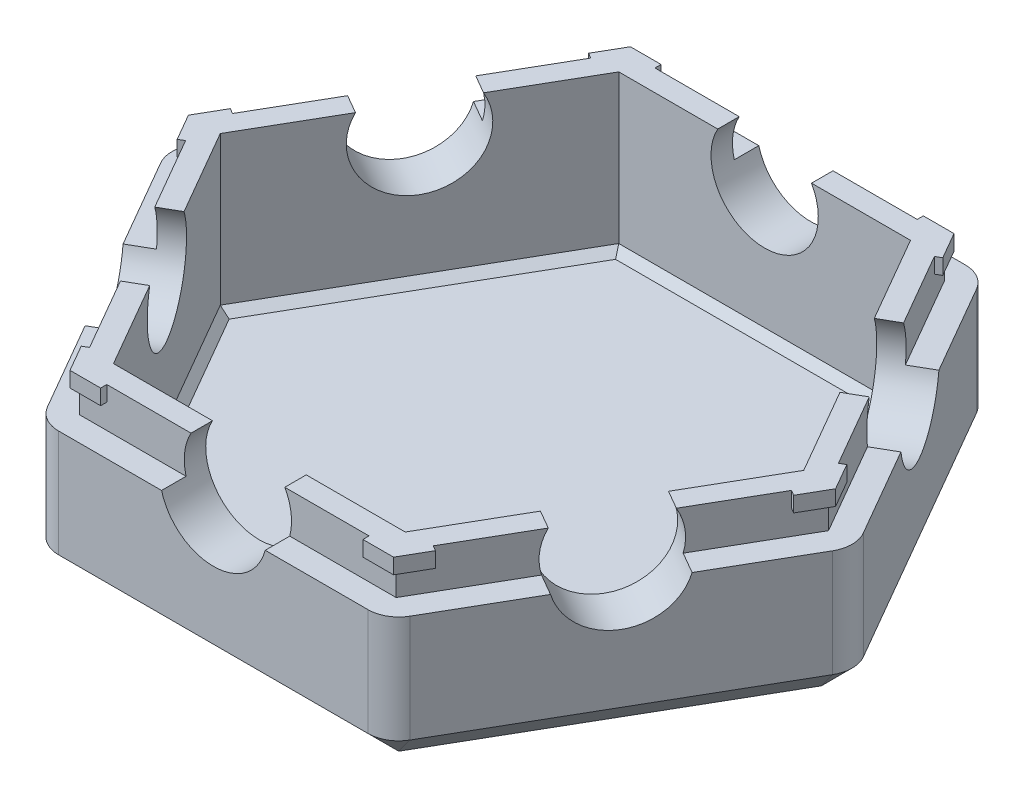
SolidWorks part; units mm, degrees
ref_plane "Front Plane" through (0, 0, 0) normal (0, 0, 1) x (1, 0, 0)
ref_plane "Top Plane" through (0, 0, 0) normal (0, 1, 0) x (1, 0, 0)
ref_plane "Right Plane" through (0, 0, 0) normal (1, 0, 0) x (0, 0, -1)
sketch "Sketch1" plane through (0, 0, 0) normal (0, 1, 0) x (1, 0, 0)
  line L0 (22.5, 0) -> (0, 0) construction
  line L1 (22.5, 0) -> (11.25, 19.4856)
  line L2 (11.25, 19.4856) -> (-11.25, 19.4856)
  line L3 (-11.25, 19.4856) -> (-22.5, 0)
  line L4 (-22.5, 0) -> (-11.25, -19.4856)
  line L5 (-11.25, -19.4856) -> (11.25, -19.4856)
  line L6 (11.25, -19.4856) -> (22.5, 0)
  circle A0 centre (0, 0) radius 19.4856 construction
  dimension "D1" = 22.5
extrude "Boss-Extrude1" add sketch "Sketch1" against normal blind 10 from offset 3.7 offset against normal yes
sketch "Sketch2" plane through (0, -3.7, 0) normal (0, 1, 0) x (1, 0, 0)
  line L0 (19.0359, 0) -> (9.5179, 16.4856)
  line L1 (9.5179, 16.4856) -> (-9.5179, 16.4856)
  line L2 (-9.5179, 16.4856) -> (-19.0359, 0)
  line L3 (-19.0359, 0) -> (-9.5179, -16.4856)
  line L4 (-9.5179, -16.4856) -> (9.5179, -16.4856)
  line L5 (9.5179, -16.4856) -> (19.0359, 0)
  line L6 (11.25, -19.4856) -> (22.5, 0)
  line L7 (22.5, 0) -> (11.25, 19.4856)
  line L8 (11.25, 19.4856) -> (-11.25, 19.4856)
  line L9 (-11.25, 19.4856) -> (-22.5, 0)
  line L10 (-22.5, 0) -> (-11.25, -19.4856)
  line L11 (-11.25, -19.4856) -> (11.25, -19.4856)
  line L12 (11.25, -19.4856) -> (22.5, 0)
  line L13 (22.5, 0) -> (11.25, 19.4856)
  line L14 (11.25, 19.4856) -> (-11.25, 19.4856)
  line L15 (-11.25, 19.4856) -> (-22.5, 0)
  line L16 (-22.5, 0) -> (-11.25, -19.4856)
  line L17 (-11.25, -19.4856) -> (11.25, -19.4856)
  dimension "D1" = 0
  dimension "D2" = 3
extrude "Cut-Extrude1" cut sketch "Sketch2" against normal blind 8.6 contours L4 L5 L0 L1 L2 L3 region at (0, -3.7, 0)
sketch "Sketch3" plane through (0, -3.7, 0) normal (0, 1, 0) x (1, 0, 0)
  line L0 (10.3262, -17.8856) -> (20.6525, 0)
  line L1 (20.6525, 0) -> (10.3262, 17.8856)
  line L2 (10.3262, 17.8856) -> (-10.3262, 17.8856)
  line L3 (-10.3262, 17.8856) -> (-20.6525, 0)
  line L4 (-20.6525, 0) -> (-10.3262, -17.8856)
  line L5 (-10.3262, -17.8856) -> (10.3262, -17.8856)
  line L6 (-9.5179, -16.4856) -> (9.5179, -16.4856)
  line L7 (-19.0359, 0) -> (-9.5179, -16.4856)
  line L8 (-9.5179, 16.4856) -> (-19.0359, 0)
  line L9 (9.5179, 16.4856) -> (-9.5179, 16.4856)
  line L10 (19.0359, 0) -> (9.5179, 16.4856)
  line L11 (9.5179, -16.4856) -> (19.0359, 0)
  line L12 (-9.5179, -16.4856) -> (9.5179, -16.4856)
  line L13 (-19.0359, 0) -> (-9.5179, -16.4856)
  line L14 (-9.5179, 16.4856) -> (-19.0359, 0)
  line L15 (9.5179, 16.4856) -> (-9.5179, 16.4856)
  line L16 (19.0359, 0) -> (9.5179, 16.4856)
  line L17 (9.5179, -16.4856) -> (19.0359, 0)
  dimension "D1" = 0
  dimension "D2" = 1.4
extrude "Boss-Extrude2" add sketch "Sketch3" along normal blind 1.6
fillet "Fillet1" radius 2 6 edges at (22.5, -8.7, 0) (11.25, -8.7, 19.4856) (-11.25, -8.7, 19.4856) (-22.5, -8.7, 0) (-11.25, -8.7, -19.4856) (11.25, -8.7, -19.4856)
sketch "Sketch6" plane through (0, -3.7, 0) normal (0, 1, 0) x (1, 0, 0)
  line L6 (10.3262, -17.8856) -> (20.6525, 0)
  line L7 (-10.3262, -17.8856) -> (10.3262, -17.8856)
  line L8 (-20.6525, 0) -> (-10.3262, -17.8856)
  line L9 (-10.3262, 17.8856) -> (-20.6525, 0)
  line L10 (10.3262, 17.8856) -> (-10.3262, 17.8856)
  line L11 (20.6525, 0) -> (10.3262, 17.8856)
  line L12 (10.3262, -17.8856) -> (20.6525, 0)
  line L13 (-10.3262, -17.8856) -> (10.3262, -17.8856)
  line L14 (-20.6525, 0) -> (-10.3262, -17.8856)
  line L15 (-10.3262, 17.8856) -> (-20.6525, 0)
  line L16 (10.3262, 17.8856) -> (-10.3262, 17.8856)
  line L17 (20.6525, 0) -> (10.3262, 17.8856)
  line L18 (11.8274, -18.4856) -> (21.9226, -1)
  line L19 (21.9226, 1) -> (11.8274, 18.4856)
  line L20 (10.0953, 19.4856) -> (-10.0953, 19.4856)
  line L21 (-11.8274, 18.4856) -> (-21.9226, 1)
  line L22 (-21.9226, -1) -> (-11.8274, -18.4856)
  line L23 (-10.0953, -19.4856) -> (10.0953, -19.4856)
  line L24 (11.8274, -18.4856) -> (21.9226, -1)
  line L25 (21.9226, 1) -> (11.8274, 18.4856)
  line L26 (10.0953, 19.4856) -> (-10.0953, 19.4856)
  line L27 (-11.8274, 18.4856) -> (-21.9226, 1)
  line L28 (-21.9226, -1) -> (-11.8274, -18.4856)
  line L29 (-10.0953, -19.4856) -> (10.0953, -19.4856)
  arc A6 (21.9226, -1) -> (21.9226, 1) centre (20.1906, 0) ccw
  arc A7 (11.8274, 18.4856) -> (10.0953, 19.4856) centre (10.0953, 17.4856) ccw
  arc A8 (-10.0953, 19.4856) -> (-11.8274, 18.4856) centre (-10.0953, 17.4856) ccw
  arc A9 (-21.9226, 1) -> (-21.9226, -1) centre (-20.1906, 0) ccw
  arc A10 (-11.8274, -18.4856) -> (-10.0953, -19.4856) centre (-10.0953, -17.4856) ccw
  arc A11 (10.0953, -19.4856) -> (11.8274, -18.4856) centre (10.0953, -17.4856) ccw
  arc A12 (21.9226, -1) -> (21.9226, 1) centre (20.1906, 0) ccw
  arc A13 (11.8274, 18.4856) -> (10.0953, 19.4856) centre (10.0953, 17.4856) ccw
  arc A14 (-10.0953, 19.4856) -> (-11.8274, 18.4856) centre (-10.0953, 17.4856) ccw
  arc A15 (-21.9226, 1) -> (-21.9226, -1) centre (-20.1906, 0) ccw
  arc A16 (-11.8274, -18.4856) -> (-10.0953, -19.4856) centre (-10.0953, -17.4856) ccw
  arc A17 (10.0953, -19.4856) -> (11.8274, -18.4856) centre (10.0953, -17.4856) ccw
  dimension "D1" = 0
  dimension "D2" = 0
extrude "Cut-Extrude4" cut sketch "Sketch6" against normal blind 1
sketch "Sketch4" plane through (0, 0, -19.4856) normal (0, 0, -1) x (-1, 0, 0)
  line L0 (0, -3.7) -> (0, -3.8) construction
  line L2 (0, -3.7) -> (0, 0) construction
  circle A0 centre (0, -3.8) radius 3.5
  dimension "D2" = 7
  dimension "D1" = 0.1
  dimension "D3" = 3.7
extrude "Cut-Extrude3" cut sketch "Sketch4" against normal up to next
ref_axis "Axis1" through (0, -14.28, 0) along (0, 1, 0)
pattern_circular "CirPattern1" count 6 every 60 about axis through (0, -14.28, 0) along (0, 1, 0) of "Cut-Extrude3"
chamfer "Chamfer1" distance 0.5 angle 45 6 edges at (-14.2769, -12.3, 8.2428) (-14.2769, -12.3, -8.2428) (0, -12.3, -16.4856) (14.2769, -12.3, -8.2428) (14.2769, -12.3, 8.2428) (0, -12.3, 16.4856)
chamfer "Chamfer2" distance 2 angle 45 12 edges at (0, -13.7, 19.4856) (11.0953, -13.7, 19.2176) (-11.0953, -13.7, 19.2176) (16.875, -13.7, 9.7428) (-16.875, -13.7, 9.7428) (22.1906, -13.7, 0) (-22.1906, -13.7, 0) (16.875, -13.7, -9.7428) (-16.875, -13.7, -9.7428) (11.0953, -13.7, -19.2176) (-11.0953, -13.7, -19.2176) (0, -13.7, -19.4856)
sketch "Sketch7" plane through (0, -2.1, 0) normal (0, 1, 0) x (1, 0, 0)
  line L124 (8.5572, 17.8856) -> (8.5572, 18.2856)
  line L125 (10.3262, 17.8856) -> (3.0594, 17.8856) construction
  line L126 (14.1446, 12.0719) -> (10.5572, 18.2856)
  line L127 (10.5572, 18.2856) -> (3.0594, 18.2856)
  line L128 (11.5572, 16.5535) -> (10.5572, 18.2856)
  line L129 (10.5572, 18.2856) -> (8.5572, 18.2856)
  line L130 (11.2108, 16.3535) -> (11.5572, 16.5535)
  line L131 (13.9597, 11.5923) -> (10.3262, 17.8856) construction
  line L132 (13.7982, 11.8719) -> (10.3262, 17.8856) construction
  line L133 (11.2108, 16.3535) -> (10.3262, 17.8856)
  line L134 (10.3262, 17.8856) -> (8.5572, 17.8856)
  line L135 (20.1144, -1.7321) -> (21.1144, 0)
  line L136 (19.7679, -1.5321) -> (20.6525, 0)
  line L137 (21.1144, 0) -> (20.1144, 1.7321)
  line L138 (20.6525, 0) -> (19.7679, 1.5321)
  line L139 (19.7679, 1.5321) -> (20.1144, 1.7321)
  line L140 (19.7679, -1.5321) -> (20.1144, -1.7321)
  line L141 (8.5572, -18.2856) -> (10.5572, -18.2856)
  line L142 (8.5572, -17.8856) -> (10.3262, -17.8856)
  line L143 (10.5572, -18.2856) -> (11.5572, -16.5535)
  line L144 (10.3262, -17.8856) -> (11.2108, -16.3535)
  line L145 (11.2108, -16.3535) -> (11.5572, -16.5535)
  line L146 (8.5572, -17.8856) -> (8.5572, -18.2856)
  line L147 (-11.5572, -16.5535) -> (-10.5572, -18.2856)
  line L148 (-11.2108, -16.3535) -> (-10.3262, -17.8856)
  line L149 (-10.5572, -18.2856) -> (-8.5572, -18.2856)
  line L150 (-10.3262, -17.8856) -> (-8.5572, -17.8856)
  line L151 (-8.5572, -17.8856) -> (-8.5572, -18.2856)
  line L152 (-11.2108, -16.3535) -> (-11.5572, -16.5535)
  line L153 (-20.1144, 1.7321) -> (-21.1144, 0)
  line L154 (-19.7679, 1.5321) -> (-20.6525, 0)
  line L155 (-21.1144, 0) -> (-20.1144, -1.7321)
  line L156 (-20.6525, 0) -> (-19.7679, -1.5321)
  line L157 (-19.7679, -1.5321) -> (-20.1144, -1.7321)
  line L158 (-19.7679, 1.5321) -> (-20.1144, 1.7321)
  line L159 (-8.5572, 18.2856) -> (-10.5572, 18.2856)
  line L160 (-8.5572, 17.8856) -> (-10.3262, 17.8856)
  line L161 (-10.5572, 18.2856) -> (-11.5572, 16.5535)
  line L162 (-10.3262, 17.8856) -> (-11.2108, 16.3535)
  line L163 (-11.2108, 16.3535) -> (-11.5572, 16.5535)
  line L164 (-8.5572, 17.8856) -> (-8.5572, 18.2856)
  point P44 (0, 0)
  dimension "D2" = 2
  dimension "D3" = 2
  dimension "D4" = 6
  dimension "D1" = 0.4
extrude "Boss-Extrude3" add sketch "Sketch7" against normal blind 1
